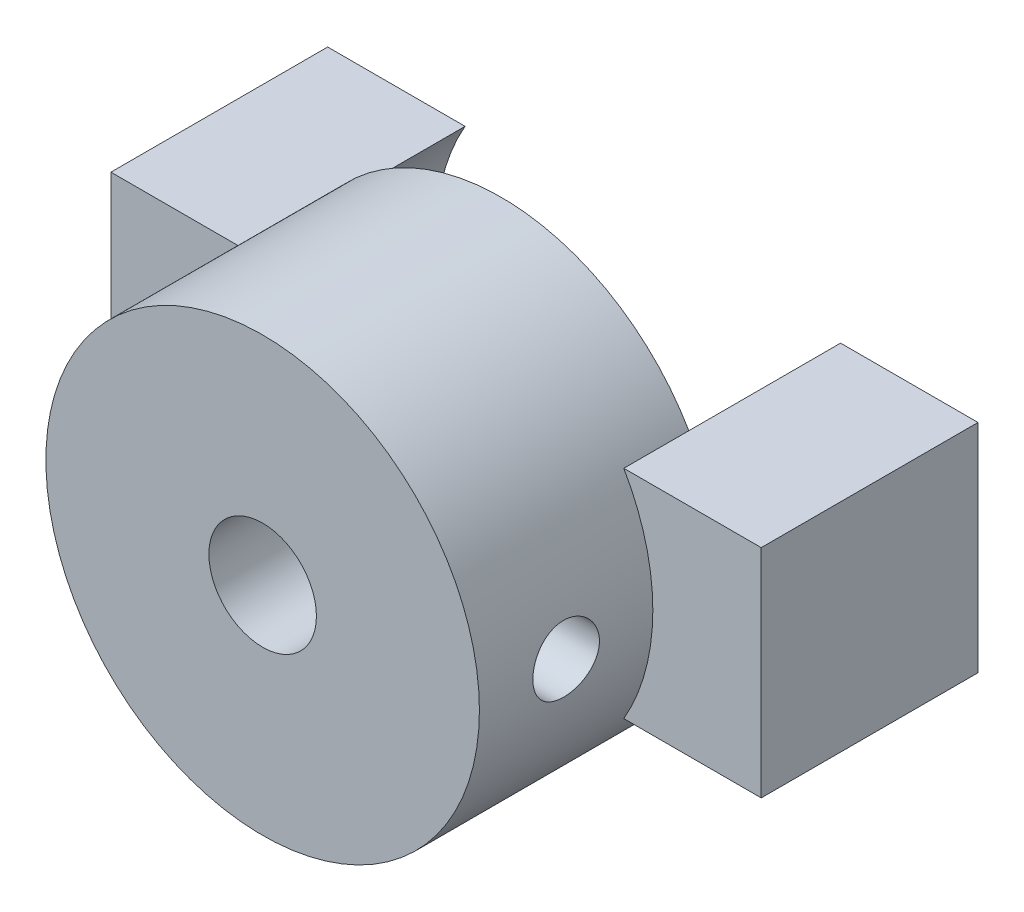
SolidWorks part; units mm, degrees
material "PLA"
ref_plane "Front Plane" through (0, 0, 0) normal (0, 0, 1) x (1, 0, 0)
ref_plane "Top Plane" through (0, 0, 0) normal (0, 1, 0) x (1, 0, 0)
ref_plane "Right Plane" through (0, 0, 0) normal (1, 0, 0) x (0, 0, -1)
sketch "Sketch1" plane through (0, 0, 0) normal (0, 0, 1) x (1, 0, 0)
  circle A0 centre (0, 0) radius 12.7
  circle A1 centre (0, 0) radius 3.15
  dimension "D1" = 25.4
  dimension "D2" = 6.3
extrude "Boss-Extrude1" add sketch "Sketch1" along normal blind 10.16
ref_plane "Plane1" through (25.4, 0, 0) normal (1, 0, 0) x (0, 0, -1)
sketch "Sketch2" plane through (25.4, 0, 0) normal (1, 0, 0) x (0, 0, -1)
  line L0 (0, -12.7) -> (0, 12.7) construction
  line L1 (-10.16, 12.7) -> (-10.16, -12.7) construction
  line L2 (0, -12.7) -> (0, 12.7)
  line L3 (-10.16, 12.7) -> (-10.16, -12.7)
  line L4 (-10.16, 0) -> (0, 0) construction
  circle A0 centre (-5.08, 0) radius 1.95
  dimension "D1" = 3.9
extrude "Cut-Extrude1" cut sketch "Sketch2" against normal up to surface (22.25 mm away) contours L4 A0 | A0 L4 region at (25.4, 0.8276, 5.08) region at (25.4, -0.8276, 5.08) up to face at (3.15, 0, 10.16)
sketch "Sketch3" plane through (0, 0, 0) normal (0, 0, -1) x (-1, 0, 0)
  line L1 (-19.05, -6.35) -> (19.05, -6.35)
  line L2 (-19.05, -6.35) -> (-19.05, 6.35)
  line L3 (-19.05, 6.35) -> (19.05, 6.35)
  line L4 (19.05, -6.35) -> (19.05, 6.35)
  line L5 (-19.05, -6.35) -> (19.05, 6.35) construction
  line L6 (-19.05, 6.35) -> (19.05, -6.35) construction
  circle A1 centre (0, 0) radius 12.7
  circle A2 centre (0, 0) radius 12.7
  circle M2 centre (0, 0) radius 12.7
  circle M3 centre (0, 0) radius 3.15
  dimension "D2" = 12.7
  dimension "D3" = 38.1
  dimension "D1" = 0
extrude "Boss-Extrude2" add sketch "Sketch3" along normal blind 6.35 contours L3 L1 M2 M3 | L3 L2 L1 M2 | L1 L4 L3 M2 | L3 M2 | L1 M2 region at (15.5812, 0, 0) region at (12.416, 0, 0) region at (0, -8.9538, 0) region at (-15.5812, 0, 0) region at (0, 8.9538, 0)
extrude "Boss-Extrude3" add sketch "Sketch3<3>" along normal blind 6.35 from surface contours L3 L2 L1 M2 | L1 L4 L3 M2 region at (15.5812, 0, 0) region at (-15.5812, 0, 0) starting at face at (0, 0, -6.35)
sketch "Sketch3<3>" plane through (0, 0, 0) normal (0, 0, -1) x (-1, 0, 0) same geometry as "Sketch3"
sketch "Sketch4" plane through (0, 0, -6.35) normal (0, 0, -1) x (-1, 0, 0)
  arc A4 (10.9985, 6.35) -> (-10.9985, 6.35) centre (0, 0) ccw
  arc A5 (-10.9985, 6.35) -> (-10.9985, -6.35) centre (0, 0) ccw
  arc A6 (-10.9985, -6.35) -> (10.9985, -6.35) centre (0, 0) ccw
  arc A7 (10.9985, -6.35) -> (10.9985, 6.35) centre (0, 0) ccw
  arc A8 (10.9985, 6.35) -> (-10.9985, 6.35) centre (0, 0) ccw
  arc A9 (-10.9985, 6.35) -> (-10.9985, -6.35) centre (0, 0) ccw
  arc A10 (-10.9985, -6.35) -> (10.9985, -6.35) centre (0, 0) ccw
  arc A11 (10.9985, -6.35) -> (10.9985, 6.35) centre (0, 0) ccw
  dimension "D1" = 0
extrude "Cut-Extrude2" cut sketch "Sketch4" against normal blind 2.54
